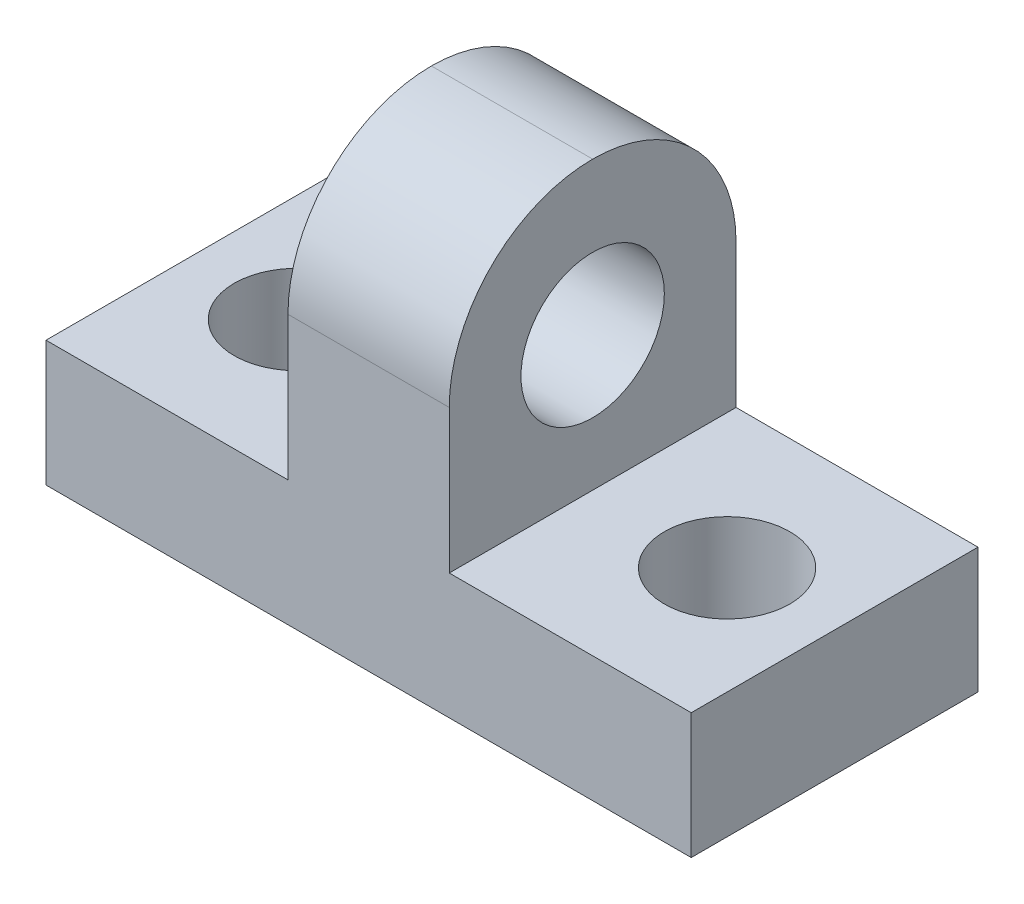
SolidWorks part; units mm, degrees
ref_plane "Front Plane" through (0, 0, 0) normal (0, 0, 1) x (1, 0, 0)
ref_plane "Top Plane" through (0, 0, 0) normal (0, 1, 0) x (1, 0, 0)
ref_plane "Right Plane" through (0, 0, 0) normal (1, 0, 0) x (0, 0, -1)
sketch "Sketch1" plane through (0, 0, 0) normal (0, 0, 1) x (1, 0, 0)
  line L0 (0, 46) -> (0, -31.6649) construction
  line L1 (36, 0) -> (-36, 0)
  line L2 (-36, 0) -> (-36, 14)
  line L3 (-36, 14) -> (-9, 14)
  line L4 (-9, 14) -> (-9, 46)
  line L5 (-9, 46) -> (9, 46)
  line L6 (9, 14) -> (9, 46)
  line L7 (36, 14) -> (9, 14)
  line L8 (36, 0) -> (36, 14)
  point P5 (0, 0)
  point P13 (0, 0)
  dimension "D1" = 72
  dimension "D2" = 14
  dimension "D3" = 32
  dimension "D4" = 18
extrude "Boss-Extrude1" add sketch "Sketch1" along normal mid plane 32
fillet "Fillet1" radius 16 2 edges at (0, 46, -16) (0, 46, 16)
sketch "Sketch6" plane through (0, 14, 0) normal (0, 1, 0) x (1, 0, 0)
  line L0 (-36, -16) -> (-36, 16) construction
  line L1 (-24, 14.0962) -> (-24, -12.6202) construction
  line L2 (-33.3586, 0) -> (-13.5058, 0) construction
  line L3 (0, 18.0077) -> (0, -10.9965) construction
  line L4 (0, -10.9965) -> (0, -13.7272) construction
  line L5 (33.3586, 0) -> (13.5058, 0) construction
  line L6 (24, 14.0962) -> (24, -12.6202) construction
  circle A0 centre (-24, 0) radius 7
  circle A1 centre (24, 0) radius 7
  dimension "D2" = 14
  dimension "D1" = 12
extrude "Cut-Extrude3" cut sketch "Sketch6" against normal blind 14
sketch "Sketch3" plane through (9, 0, 0) normal (1, 0, 0) x (0, 0, -1)
  line L0 (0, 39.3255) -> (0, 18.4623) construction
  line L1 (-11.09, 29) -> (10.6409, 29) construction
  circle A1 centre (0, 29) radius 8
  dimension "D1" = 17
  dimension "D2" = 16
extrude "Cut-Extrude2" cut sketch "Sketch3" against normal blind 18
